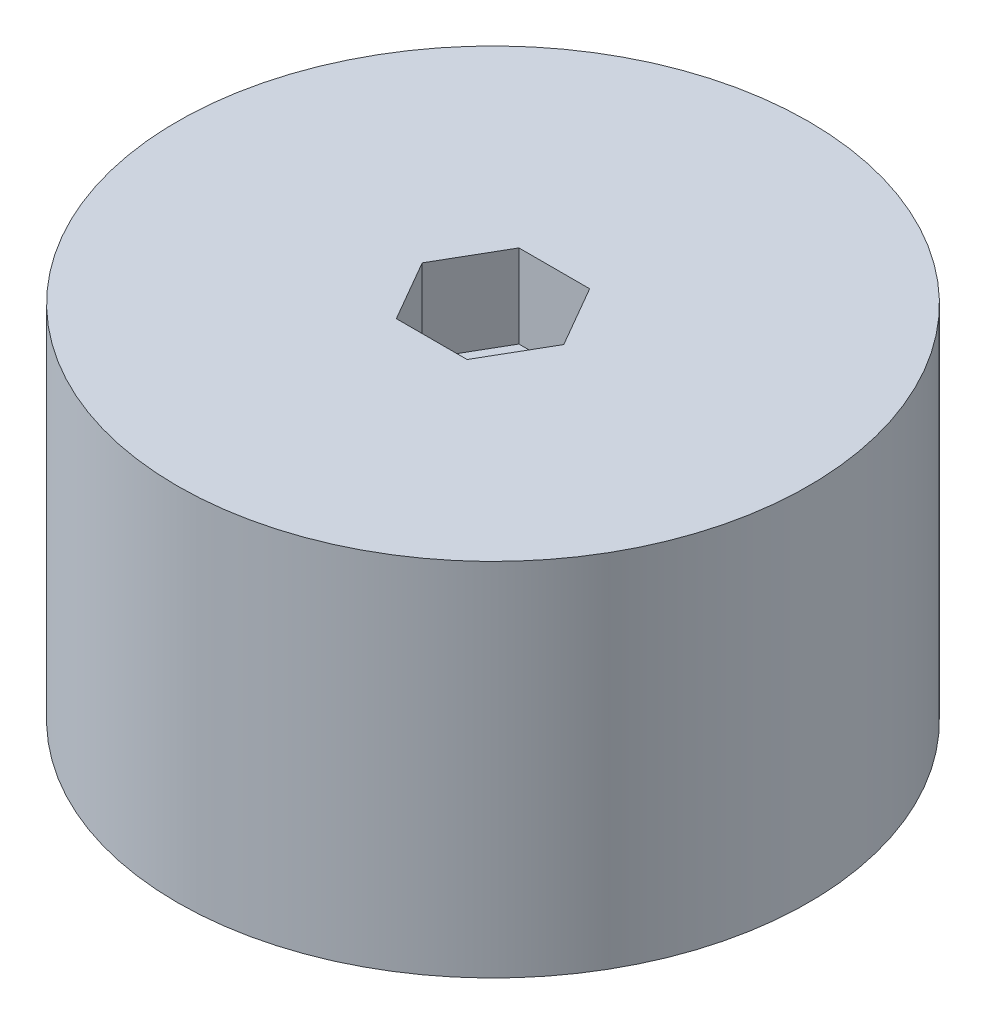
SolidWorks part; units mm, degrees
ref_plane "Front Plane" through (0, 0, 0) normal (0, 0, 1) x (1, 0, 0)
ref_plane "Top Plane" through (0, 0, 0) normal (0, 1, 0) x (1, 0, 0)
ref_plane "Right Plane" through (0, 0, 0) normal (1, 0, 0) x (0, 0, -1)
sketch "Sketch1" plane through (0, 0, 0) normal (0, 1, 0) x (1, 0, 0)
  circle A0 centre (0, 0) radius 22.75
  circle A1 centre (0, 0) radius 2.5
  dimension "D1" = 45.5
  dimension "D2" = 5
extrude "Boss-Extrude1" add sketch "Sketch1" along normal blind 26
sketch "Sketch2" plane through (0, 26, 0) normal (0, 1, 0) x (1, 0, 0)
  line L1 (5.1, 0) -> (2.55, 4.4167)
  line L2 (2.55, 4.4167) -> (-2.55, 4.4167)
  line L3 (-2.55, 4.4167) -> (-5.1, 0)
  line L4 (-5.1, 0) -> (-2.55, -4.4167)
  line L5 (-2.55, -4.4167) -> (2.55, -4.4167)
  line L6 (2.55, -4.4167) -> (5.1, 0)
  circle A0 centre (0, 0) radius 4.4167 construction
  dimension "D1" = 5.1
extrude "Cut-Extrude1" cut sketch "Sketch2" against normal blind 6
